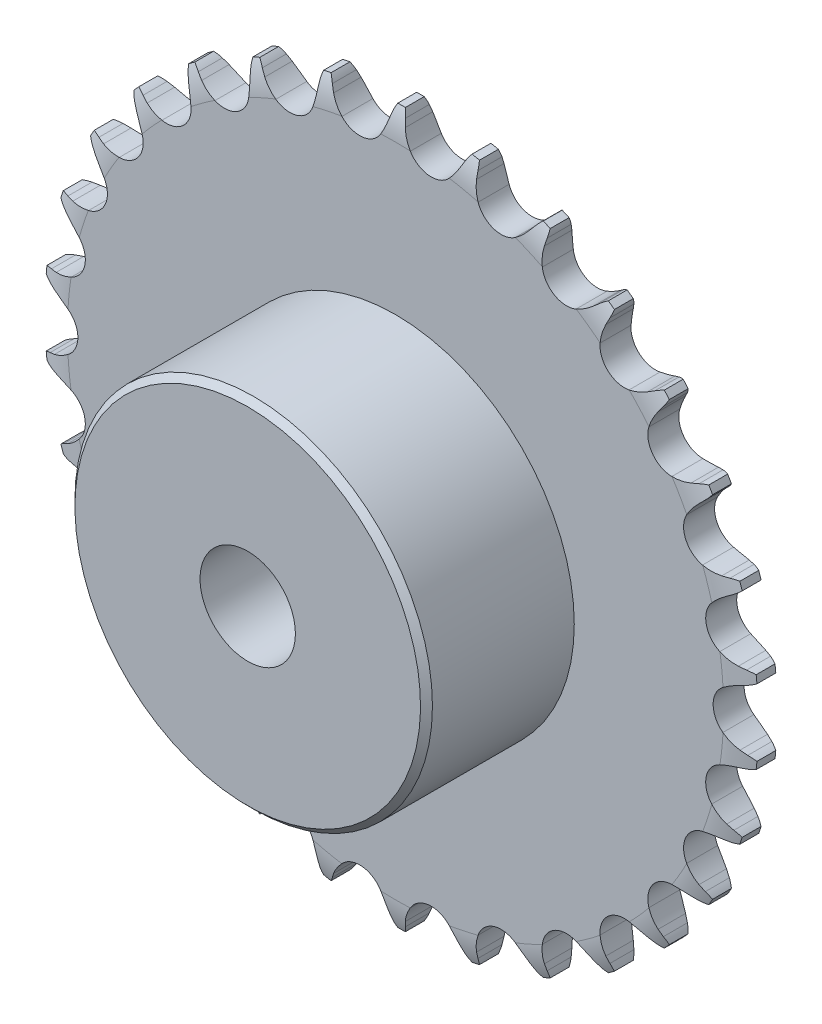
SolidWorks part; units mm, degrees
ref_plane "Front Plane" through (0, 0, 0) normal (0, 0, 1) x (1, 0, 0)
ref_plane "Top Plane" through (0, 0, 0) normal (0, 1, 0) x (1, 0, 0)
ref_plane "Right Plane" through (0, 0, 0) normal (1, 0, 0) x (0, 0, -1)
sketch "Sketch0" plane through (0, 0, 0) normal (0, 0, 1) x (1, 0, 0)
  line L0 (3, -28.5431) -> (0, 0) construction
  line L1 (0, 0) -> (8.8689, -27.2956) construction
  line L2 (0, 0) -> (-3, -28.5431) construction
  line L3 (3, -28.5431) -> (8.8689, -27.2956) construction
  line L4 (3, -28.5431) -> (-3, -28.5431) construction
  line L5 (5.5888, -28.8423) -> (5.3413, -28.3538)
  line L6 (3, -28.5431) -> (0, -28.8584) construction
  line L7 (0.53, -29.374) -> (0.6705, -28.8447)
  line L8 (0, -28.5431) -> (0, -30.3431) construction
  line L9 (4.4979, -27.1463) -> (0.6597, -30.7255) construction
  line L10 (0, 0) -> (0, -28.5431) construction
  line L11 (5.3413, -28.3538) -> (0.6597, -30.7255) construction
  line L12 (0, -30.3431) -> (0, -30.4737) construction
  line L13 (8.4776, -27.3788) -> (5.5888, -28.8423) construction
  circle A0 centre (0, 0) radius 30.3431 construction
  circle A1 centre (0, 0) radius 28.7003 construction
  arc A2 (-2.8938, -31.7682) -> (9.4355, -30.4723) centre (0, 0) ccw
  circle A3 centre (0, 0) radius 30.4737 construction
  circle A4 centre (3, -28.5431) radius 2 construction
  arc A7 (4.4979, -27.1463) -> (1.2444, -27.4882) centre (3, -28.5431) ccw
  circle A8 centre (3, -28.5431) radius 2.0481 construction
  arc A9 (5.5888, -28.8423) -> (9.4355, -30.4723) centre (8.4776, -27.3788) ccw
  arc A10 (5.3413, -28.3538) -> (4.4979, -27.1463) centre (0.6597, -30.7255) ccw
  arc A11 (0.53, -29.374) -> (-2.8938, -31.7682) centre (-2.6, -28.5431) cw
  arc A12 (0.6705, -28.8447) -> (1.2444, -27.4882) centre (5.7429, -30.1912) cw
  dimension "D1" = 2.0481
  dimension "R" = 2.0481
sketch "Sketch1" plane through (0, 0, 0) normal (1, 0, 0) x (0, 0, -1)
  line L0 (1.3, 0) -> (-1.3, 0)
  line L1 (-1.3, 0) -> (-1.3, 27.5306)
  line L2 (-1.3, 28.7003) -> (0, 28.7003) construction
  line L3 (-0.6, 30.3431) -> (0.6, 30.3431)
  line L5 (1.3, 27.5306) -> (1.3, 0)
  line L7 (0, 30.3431) -> (0, 0) construction
  line L8 (-1.3, 27.5306) -> (1.3, 27.5306) construction
  line L9 (0, 30.3431) -> (0, -30.3431) construction
  line L10 (-1.3, 27.5306) -> (-1.3, 30.3431) construction
  line L11 (-1.3, 30.3431) -> (-0.6, 30.3431) construction
  line L12 (0.6, 30.3431) -> (1.3, 30.3431) construction
  line L13 (1.3, 30.3431) -> (1.3, 27.5306) construction
  line L14 (0, 0) -> (-6.4008, 0) construction
  line L15 (-1.3, 28.7003) -> (-1.3, 24.6003) construction
  line L22 (1.3, 0) -> (-13.7, 0) construction
  line L24 (-1.3, 0) -> (-1.3, 24.6003) construction
  arc A0 (-0.6, 30.3431) -> (-1.3, 27.5306) centre (4.7, 27.5306) ccw
  arc A1 (0.6, 30.3431) -> (1.3, 27.5306) centre (-4.7, 27.5306) cw
  dimension "R" = 6
revolve "Revolve1" add sketch "Sketch1" angle 360 mid plane about L0
extrude "Cut-Extrude1" cut sketch "Sketch0" against normal through all and the other way through all
pattern_circular "CirPattern1" count 30 over 360 about axis through (0, 0, -1.3) along (0, 0, -1) of "Cut-Extrude1"
sketch "Sketch2" plane through (0, 0, 0) normal (0, 0, 1) x (1, 0, 0)
  circle A0 centre (0, 0) radius 4 construction
  circle A1 centre (0, 0) radius 15
  circle A2 centre (0, 0) radius 29.95 construction
  dimension "Bore" = 8
  dimension "Hub Dia." = 30
  dimension "OD" = 59.9
extrude "Boss-Extrude1" add sketch "Sketch2" along normal up to vertex (13.7 mm away) from surface up to point (0, 0, 13.7) starting at face at (0, 0, 1.3)
sketch "Sketch3" plane through (0, 0, 0) normal (0, 0, 1) x (1, 0, 0)
  circle A0 centre (0, 0) radius 4 construction
  circle A1 centre (0, 0) radius 4
extrude "Cut-Extrude2" cut sketch "Sketch3" along normal through all and the other way through all
sketch "Sketch4" plane through (0, 0, 0) normal (1, 0, 0) x (0, 0, -1)
  line L0 (-13.7, 15) -> (-13.7, 14.5)
  line L1 (-1.3, 30.3431) -> (-3.25, 30.3431)
  line L2 (-1.3, 30.3431) -> (-1.3, 24.6003)
  line L3 (-1.3, 24.6003) -> (-3.25, 24.6003)
  line L4 (-3.25, 30.3431) -> (-3.25, 24.6003)
  line L9 (-13.7, 14.5) -> (-13.2, 15)
  line L10 (-13.2, 15) -> (-13.7, 15)
  dimension "C" = 0.5
  dimension "D3" = 1.95
revolve "Cut-Revolve1" cut sketch "Sketch4" angle 360 mid plane about L22
sketch "Sketch5" plane through (0, 0, 0) normal (0, 0, 1) x (1, 0, 0)
  circle A0 centre (0, 0) radius 29.95 construction
  circle A1 centre (0, 0) radius 29.95
extrude "Cut-Extrude3" cut sketch "Sketch5" against normal through all and the other way through all flip side to cut
equation "\"360/N@Sketch0\" = 360/\"Teeth@CirPattern1\""
equation "\"Ds@Sketch0\" = 1.005 * \"Dr@Sketch0\" + ( 0.003 * 25.4 ) "
equation "\"R@Sketch0\" = 1/2 * \"Ds@Sketch0\""
equation "\"A@Sketch0\" = 35 +  ( 60 / \"Teeth@CirPattern1\" ) "
equation "\"B@Sketch0\" = 18 -  ( 56 / \"Teeth@CirPattern1\" )"
equation "\"ac@Sketch0\" = 0.8 * \"Dr@Sketch0\""
equation "\"ab@Sketch0\" = 1.4 * \"Dr@Sketch0\""
equation "\"J@Sketch0\" = 0.3 * \"Pitch@Sketch0\""
equation "\"D3@Sketch4\" = \"t@Sketch1\" * 3 / 4"
